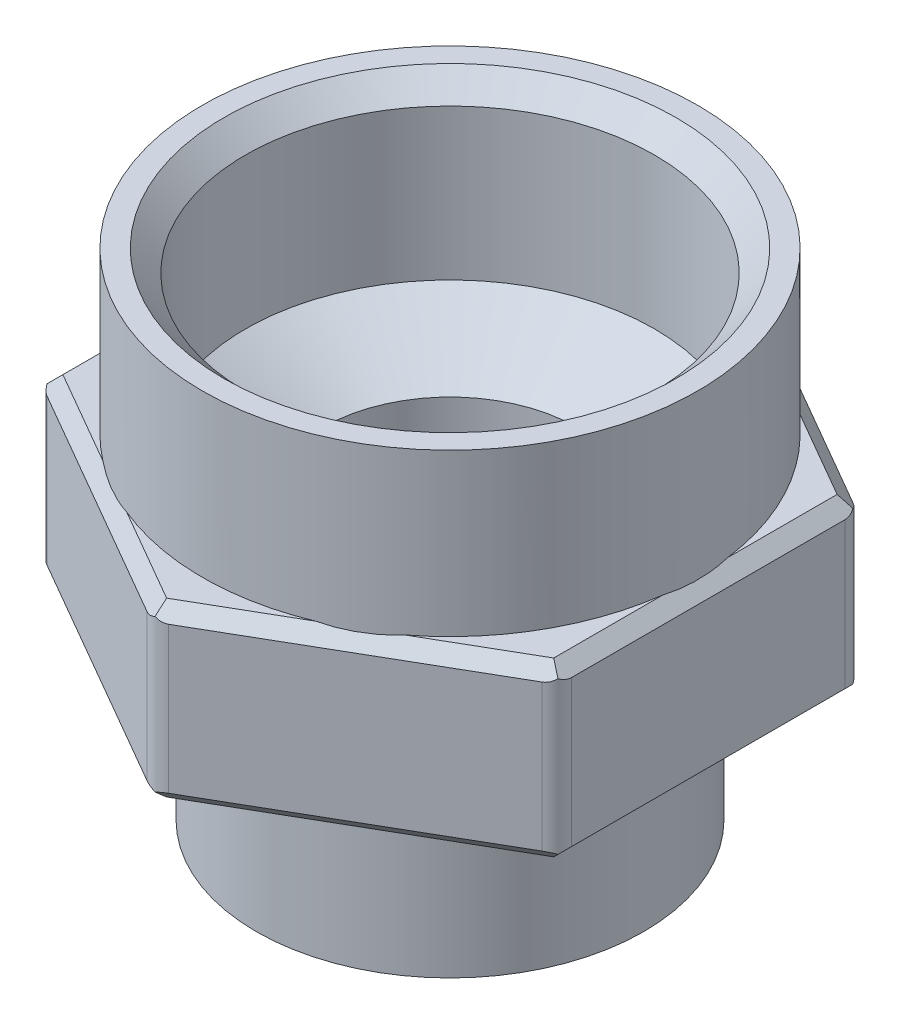
SolidWorks part; units mm, degrees
ref_plane "Спереди" through (0, 0, 0) normal (0, 0, 1) x (1, 0, 0)
ref_plane "Сверху" through (0, 0, 0) normal (0, 1, 0) x (1, 0, 0)
ref_plane "Справа" through (0, 0, 0) normal (1, 0, 0) x (0, 0, -1)
sketch "Эскиз1" plane through (0, 0, 0) normal (0, 1, 0) x (1, 0, 0)
  circle A1 centre (0, 0) radius 9
  dimension "D1" = 18
extrude "Бобышка-Вытянуть1" add sketch "Эскиз1" along normal blind 7.5
sketch "Эскиз2" plane through (0, 7.5, 0) normal (0, 1, 0) x (1, 0, 0)
  line L1 (0, 13.8564) -> (-12, 6.9282)
  line L2 (-12, 6.9282) -> (-12, -6.9282)
  line L3 (-12, -6.9282) -> (0, -13.8564)
  line L4 (0, -13.8564) -> (12, -6.9282)
  line L5 (12, -6.9282) -> (12, 6.9282)
  line L6 (12, 6.9282) -> (0, 13.8564)
  circle A2 centre (0, 0) radius 13.8564 construction
  circle A3 centre (0, 0) radius 12 construction
  dimension "D1" = 24
extrude "Бобышка-Вытянуть2" add sketch "Эскиз2" along normal blind 8 contours L1 L2 L3 L4 L5 L6
sketch "Эскиз3" plane through (0, 15.5, 0) normal (0, 1, 0) x (1, 0, 0)
  circle A1 centre (0, 0) radius 11.5
  dimension "D1" = 23
extrude "Бобышка-Вытянуть3" add sketch "Эскиз3" along normal blind 7.5
chamfer "Фаска2" distance 0.6 angle 45 12 edges at (6, 7.5, -10.3923) (12, 7.5, 0) (6, 7.5, 10.3923) (-6, 7.5, 10.3923) (-12, 7.5, 0) (-6, 7.5, -10.3923) (-6, 15.5, 10.3923) (-12, 15.5, 0) (-6, 15.5, -10.3923) (6, 15.5, -10.3923) (12, 15.5, 0) (6, 15.5, 10.3923)
fillet "Скругление1" radius 1 6 edges at (12, 11.5, 6.9282) (12, 11.5, -6.9282) (0, 11.5, -13.8564) (-12, 11.5, -6.9282) (-12, 11.5, 6.9282) (0, 11.5, 13.8564)
hole_wizard "Отверстие обработанное метчиком G1/22" positions "Эскиз8" profile "Эскиз9" tap size "G1/2" standard "ISO"
sketch "Эскиз8" plane through (0, 23, 0) normal (0, 1, 0) x (1, 0, 0)
  point P0 (0, 0)
sketch "Эскиз9" plane through (0, 23, 0) normal (1, 0, 0) x (0, 0, 1)
  line L0 (0, 0) -> (0, 13.7082)
  line L1 (0, 13.7082) -> (9.5, 8)
  line L2 (9.5, 8) -> (9.5, 1.0025)
  line L3 (9.5, 1.0025) -> (10.5025, 0)
  line L5 (10.5025, 0) -> (0, 0)
  line L6 (-9.5, 1.0025) -> (-10.5025, 0) construction
  line L10 (0, 13.7082) -> (-9.5, 8) construction
  line L11 (0, -6.35) -> (0, 107.95) construction
  dimension "Диаметр сверла" = 19
  dimension "Глубина сверла" = 8
  dimension "Диаметр передней зенковки" = 21.005
  dimension "Угол передней зенковки" = 90
  dimension "Угол заточки сверла" = 118
cosmetic thread "Отверстие резьбы1" parameters "D1"=8, "D2"=20.955
hole_wizard "Отверстие обработанное метчиком G1/41" positions "Эскиз10" profile "Эскиз11" tap size "G1/4" standard "ISO"
sketch "Эскиз10" plane through (0, 0, 0) normal (0, -1, 0) x (-1, 0, 0)
  point P0 (0, 0)
sketch "Эскиз11" plane through (0, 0, 0) normal (1, 0, 0) x (0, 0, -1)
  line L0 (0, 0) -> (0, 33.8651)
  line L1 (0, 33.8651) -> (5.9, 30.32)
  line L2 (5.9, 30.32) -> (5.9, 0.7035)
  line L3 (5.9, 0.7035) -> (6.6035, 0)
  line L5 (6.6035, 0) -> (0, 0)
  line L6 (-5.9, 0.7035) -> (-6.6035, 0) construction
  line L10 (0, 33.8651) -> (-5.9, 30.32) construction
  line L11 (0, -6.35) -> (0, 107.95) construction
  dimension "Диаметр сверла" = 11.8
  dimension "Глубина сверла" = 30.32
  dimension "Диаметр передней зенковки" = 13.207
  dimension "Угол передней зенковки" = 90
  dimension "Угол заточки сверла" = 118
cosmetic thread "Отверстие резьбы2" parameters "D1"=11.5, "D2"=13.157
